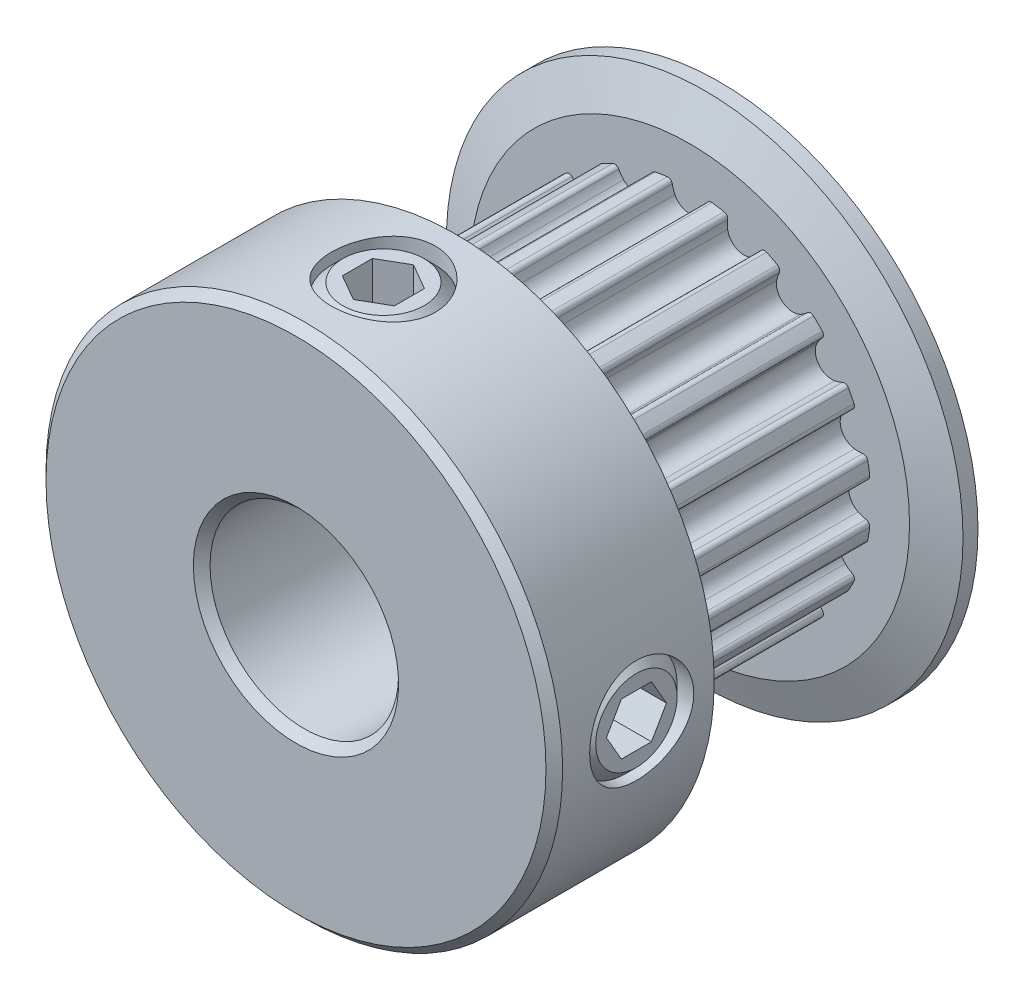
SolidWorks part; units mm, degrees
ref_plane "Front Plane" through (0, 0, 0) normal (0, 0, 1) x (1, 0, 0)
ref_plane "Top Plane" through (0, 0, 0) normal (0, 1, 0) x (1, 0, 0)
ref_plane "Right Plane" through (0, 0, 0) normal (1, 0, 0) x (0, 0, -1)
sketch "Sketch1" plane through (0, 0, 0) normal (0, 0, 1) x (1, 0, 0)
  line L1 (-1.7499, 5.3585) -> (1.7499, 5.3585) construction
  line L4 (0, 0) -> (0, 5.3585) construction
  line L5 (0, 5.3585) -> (0, 11.2144) construction
  line L6 (0, 6.3625) -> (1.9751, 6.0482) construction
  line L7 (1.9751, 6.0482) -> (2.6648, 5.8229) construction
  line L8 (1.9751, 6.0482) -> (1.7499, 5.3585) construction
  line L9 (-1.9751, 6.0482) -> (-1.7499, 5.3585) construction
  line L10 (-1.8963, 5.8067) -> (-2.841, 8.6995)
  line L11 (-2.841, 8.6995) -> (2.841, 8.6995)
  line L12 (2.841, 8.6995) -> (1.8963, 5.8067)
  circle A0 centre (0, 0) radius 6.3625 construction
  circle A1 centre (0, 0) radius 8.6995 construction
  circle A2 centre (0, 0) radius 6.1085 construction
  arc A3 (-0.4989, 5.6703) -> (0.4989, 5.6703) centre (0, 5.9135) ccw
  arc A4 (-0.4989, 5.6703) -> (-0.5855, 5.9387) centre (0.4, 6.1085) cw
  arc A5 (-1.8963, 5.8067) -> (-0.7518, 6.0621) centre (0, 0) cw
  arc A6 (-0.5855, 5.9387) -> (-0.7518, 6.0621) centre (-0.7333, 5.9132) ccw
  arc A7 (1.8963, 5.8067) -> (0.7518, 6.0621) centre (0, 0) ccw
  arc A8 (0.5855, 5.9387) -> (0.7518, 6.0621) centre (0.7333, 5.9132) cw
  arc A9 (0.4989, 5.6703) -> (0.5855, 5.9387) centre (-0.4, 6.1085) ccw
  point P6 (0, 20.9083)
  point P11 (0, 6.3625)
  point P13 (0, 8.6995)
  point P14 (0, 6.1085)
  dimension "D1" = 9.6939
  dimension "D2" = 4.8519
sketch "Sketch2" plane through (0, 0, 0) normal (1, 0, 0) x (0, 0, -1)
  line L0 (-7.135, 3.175) -> (7.135, 3.175)
  line L1 (-7.135, 3.175) -> (-7.135, 8.6995)
  line L2 (-1.75, 8.6995) -> (-7.135, 8.6995)
  line L3 (-2.255, 3.175) -> (-2.255, 8.6995) construction
  line L4 (-2.255, 8.6995) -> (-1.245, 8.6995) construction
  line L5 (-1.245, 8.6995) -> (-1.245, 6.1085) construction
  line L6 (-1.245, 6.1085) -> (6.125, 6.1085)
  line L7 (6.125, 6.1085) -> (6.125, 8.6995) construction
  line L8 (6.125, 8.6995) -> (7.135, 8.6995) construction
  line L9 (7.135, 8.6995) -> (7.135, 3.175)
  line L10 (-7.135, 0) -> (7.135, 0) construction
  line L11 (6.63, 8.6995) -> (6.125, 7.404)
  line L12 (-1.245, 7.404) -> (-1.75, 8.6995)
  line L14 (-1.245, 7.404) -> (-1.245, 6.1085)
  line L15 (6.125, 6.1085) -> (6.125, 7.404)
  line L16 (6.63, 8.6995) -> (7.135, 8.6995)
  arc A0 (-1.245, 7.404) -> (-1.75, 8.6995) centre (-3.1592, 7.404) ccw construction
  arc A1 (6.125, 7.404) -> (6.63, 8.6995) centre (8.0392, 7.404) cw construction
  point P12 (-1.245, 7.404)
  point P14 (-1.75, 8.6995)
  point P20 (6.125, 7.404)
  point P21 (6.63, 8.6995)
  point P25 (6.125, 0)
  point P26 (-1.245, 0)
  dimension "OA" = 14.27
  dimension "Bore" = 6.35
  dimension "Outside Width" = 8.38
  dimension "Inside Width" = 7.37
revolve "Revolve1" add sketch "Sketch2" angle 360 mid plane about L10
sketch "Sketch3" plane through (0, 0, 0) normal (0, 0, 1) x (1, 0, 0)
  line L6 (2.841, 8.6995) -> (-2.841, 8.6995)
  line L7 (1.8963, 5.8067) -> (2.841, 8.6995)
  line L8 (-2.841, 8.6995) -> (-1.8963, 5.8067)
  line L9 (2.841, 8.6995) -> (-2.841, 8.6995)
  line L10 (1.8963, 5.8067) -> (2.841, 8.6995)
  line L11 (-2.841, 8.6995) -> (-1.8963, 5.8067)
  arc A8 (1.8963, 5.8067) -> (0.7518, 6.0621) centre (0, 0) ccw
  arc A9 (0.7518, 6.0621) -> (0.5855, 5.9387) centre (0.7333, 5.9132) ccw
  arc A10 (0.4989, 5.6703) -> (0.5855, 5.9387) centre (-0.4, 6.1085) ccw
  arc A11 (-0.4989, 5.6703) -> (0.4989, 5.6703) centre (0, 5.9135) ccw
  arc A12 (-0.5855, 5.9387) -> (-0.4989, 5.6703) centre (0.4, 6.1085) ccw
  arc A13 (-0.5855, 5.9387) -> (-0.7518, 6.0621) centre (-0.7333, 5.9132) ccw
  arc A14 (-0.7518, 6.0621) -> (-1.8963, 5.8067) centre (0, 0) ccw
  arc A15 (1.8963, 5.8067) -> (0.7518, 6.0621) centre (0, 0) ccw
  arc A16 (0.7518, 6.0621) -> (0.5855, 5.9387) centre (0.7333, 5.9132) ccw
  arc A17 (0.4989, 5.6703) -> (0.5855, 5.9387) centre (-0.4, 6.1085) ccw
  arc A18 (-0.4989, 5.6703) -> (0.4989, 5.6703) centre (0, 5.9135) ccw
  arc A19 (-0.5855, 5.9387) -> (-0.4989, 5.6703) centre (0.4, 6.1085) ccw
  arc A20 (-0.5855, 5.9387) -> (-0.7518, 6.0621) centre (-0.7333, 5.9132) ccw
  arc A21 (-0.7518, 6.0621) -> (-1.8963, 5.8067) centre (0, 0) ccw
  dimension "D1" = 0
extrude "Cut-Extrude1" cut sketch "Sketch3" against normal up to vertex (6.125 mm away) from vertex up to point (0, 6.1085, -6.125) starting at point (0, 6.1085, 1.245)
pattern_circular "CirPattern1" count 20 over 360 about axis through (0, 0, 7.135) along (0, 0, 1) of "Cut-Extrude1"
sketch "Sketch4" plane through (0, 0, 0) normal (1, 0, 0) x (0, -1, 0)
  line L0 (0, -1.245) -> (0, -7.135) construction
  line L1 (-3.175, -7.135) -> (3.175, -7.135) construction
  line L2 (7.404, -1.245) -> (-7.404, -1.245) construction
  circle A0 centre (0, -4.19) radius 1.7526
extrude "Cut-Extrude2" cut sketch "Sketch4" along normal through all
ref_plane "Plane1" through (0, 0, 4.19) normal (0, 0, 1) x (1, 0, 0)
sketch "Sketch5" plane through (0, 0, 4.19) normal (0, 0, 1) x (1, 0, 0)
  line L0 (0, 0) -> (0, 8.6995) construction
  line L1 (3.175, -1.3716) -> (3.175, 0)
  line L2 (3.556, -1.7526) -> (8.1401, -1.7526)
  line L3 (3.175, 0) -> (8.6995, 0) construction
  line L4 (3.175, 0) -> (8.5211, 0)
  line L5 (8.5211, 0) -> (8.5211, -1.3716)
  line L6 (3.556, -1.7526) -> (3.175, -1.3716)
  line L7 (8.5211, -1.3716) -> (8.1401, -1.7526)
  circle A0 centre (0, 0) radius 8.6995 construction
  circle A1 centre (0, 0) radius 3.175 construction
  point P2 (3.175, -1.7526)
  point P11 (8.5211, -1.7526)
revolve "Revolve2" add sketch "Sketch5" angle 360 mid plane about L4
sketch "Sketch6" plane through (8.5211, 5.3841, 0) normal (-1, 0, 0) x (0, -1, 0)
  line L1 (5.3841, 5.2019) -> (4.5078, 4.6959)
  line L2 (4.5078, 4.6959) -> (4.5078, 3.6841)
  line L3 (4.5078, 3.6841) -> (5.3841, 3.1781)
  line L4 (5.3841, 3.1781) -> (6.2604, 3.6841)
  line L5 (6.2604, 3.6841) -> (6.2604, 4.6959)
  line L6 (6.2604, 4.6959) -> (5.3841, 5.2019)
  circle A0 centre (5.3841, 4.19) radius 0.8763 construction
  dimension "D1" = 1.7526
extrude "Cut-Extrude3" cut sketch "Sketch6" along normal blind 1.3144
pattern_circular "CirPattern3" count 2 over 90 about axis through (0, 0, 7.135) along (0, 0, 1) of "Cut-Extrude2", "Revolve2", "Cut-Extrude3"
chamfer "Chamfer1" distance 0.2807 angle 45 2 edges at (3.175, 0, 7.135) (8.6995, 0, 7.135)
ref_axis "Center Axis 1" through (0, 0, -7.135) along (0, 0, 1)
ref_plane "Contact Plane 1" through (0, 0, 7.135) normal (0, 0, 1) x (1, 0, 0)
ref_plane "Contact Plane 2" through (0, 0, -7.135) normal (0, 0, -1) x (-1, 0, 0)
equation "\"D2@Sketch1\"= \"D1@Sketch1\" / 2"
equation "\"D1@Sketch6\" = \"Set Screw@Sketch4\" / 2"
equation "\"D1@Cut-Extrude3\" = \"D1@Sketch6\"*.75"
